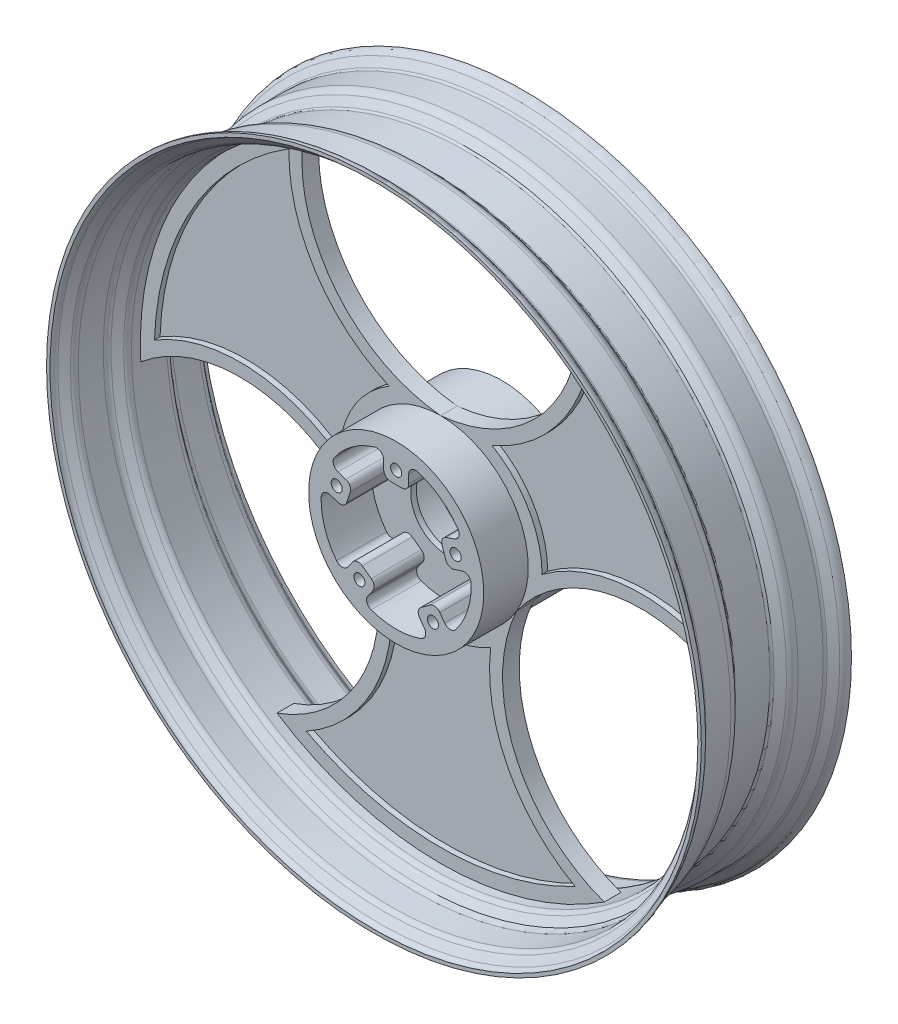
SolidWorks part; units mm, degrees
ref_plane "Front Plane" through (0, 0, 0) normal (0, 0, 1) x (1, 0, 0)
ref_plane "Top Plane" through (0, 0, 0) normal (0, 1, 0) x (1, 0, 0)
ref_plane "Right Plane" through (0, 0, 0) normal (1, 0, 0) x (0, 0, -1)
sketch "Sketch1" plane through (0, 0, 0) normal (1, 0, 0) x (0, 0, -1)
  line L0 (0, 106.096) -> (0, -87.6732) construction
  line L1 (-108.1057, 0) -> (149.1229, 0) construction
  line L27 (-38, 0) -> (38, 0)
  line L28 (38, 0) -> (38, 63)
  line L29 (-38, 0) -> (-38, 63)
  line L30 (38, 63) -> (6, 63)
  line L31 (-38, 63) -> (-6, 63)
  line L32 (6, 63) -> (6, 216)
  line L33 (-6, 63) -> (-6, 216)
  line L34 (6, 216) -> (12.4092, 216)
  line L35 (-6, 216) -> (-12.4092, 216)
  line L36 (16.2394, 217.7861) -> (20.3744, 222.7139)
  line L37 (-16.2394, 217.7861) -> (-20.3744, 222.7139)
  line L38 (24.2046, 224.5) -> (42.2046, 224.5)
  line L39 (-24.2046, 224.5) -> (-42.2046, 224.5)
  line L40 (46.0348, 226.2861) -> (50.1698, 231.2139)
  line L41 (-46.0348, 226.2861) -> (-50.1698, 231.2139)
  line L42 (54, 233) -> (54, 235.5)
  line L43 (-54, 233) -> (-54, 235.5)
  line L44 (48.2547, 232.8209) -> (44.1197, 227.893)
  line L45 (-48.2547, 232.8209) -> (-44.1197, 227.893)
  line L46 (42.2046, 227) -> (24.2046, 227)
  line L47 (-42.2046, 227) -> (-24.2046, 227)
  line L48 (18.4592, 224.3209) -> (14.3243, 219.393)
  line L49 (-18.4592, 224.3209) -> (-14.3243, 219.393)
  line L50 (12.4092, 218.5) -> (0, 218.5)
  line L51 (-12.4092, 218.5) -> (0, 218.5)
  arc A16 (12.4092, 216) -> (16.2394, 217.7861) centre (12.4092, 221) ccw
  arc A17 (-12.4092, 216) -> (-16.2394, 217.7861) centre (-12.4092, 221) cw
  arc A18 (20.3744, 222.7139) -> (24.2046, 224.5) centre (24.2046, 219.5) cw
  arc A19 (-20.3744, 222.7139) -> (-24.2046, 224.5) centre (-24.2046, 219.5) ccw
  arc A20 (42.2046, 224.5) -> (46.0348, 226.2861) centre (42.2046, 229.5) ccw
  arc A21 (-42.2046, 224.5) -> (-46.0348, 226.2861) centre (-42.2046, 229.5) cw
  arc A22 (50.1698, 231.2139) -> (54, 233) centre (54, 228) cw
  arc A23 (-50.1698, 231.2139) -> (-54, 233) centre (-54, 228) ccw
  arc A24 (54, 235.5) -> (48.2547, 232.8209) centre (54, 228) ccw
  arc A25 (-54, 235.5) -> (-48.2547, 232.8209) centre (-54, 228) cw
  arc A26 (44.1197, 227.893) -> (42.2046, 227) centre (42.2046, 229.5) cw
  arc A27 (-44.1197, 227.893) -> (-42.2046, 227) centre (-42.2046, 229.5) ccw
  arc A28 (24.2046, 227) -> (18.4592, 224.3209) centre (24.2046, 219.5) ccw
  arc A29 (-24.2046, 227) -> (-18.4592, 224.3209) centre (-24.2046, 219.5) cw
  arc A30 (14.3243, 219.393) -> (12.4092, 218.5) centre (12.4092, 221) cw
  arc A31 (-14.3243, 219.393) -> (-12.4092, 218.5) centre (-12.4092, 221) ccw
  point P8 (0, 0)
  dimension "D2" = 76
  dimension "D11" = 5
  dimension "D1" = 2.5
  dimension "D3" = 32
  dimension "D4" = 63
  dimension "D5" = 432
  dimension "D6" = 50
  dimension "D7" = 54
  dimension "D8" = 18
  dimension "D9" = 8.5
  dimension "D10" = 8.5
revolve "Revolve1" add sketch "Sketch1" angle 360 about L1
sketch "Sketch2" plane through (0, 0, 6) normal (0, 0, 1) x (1, 0, 0)
  line L0 (0, 278.9193) -> (0, -275.6484) construction
  arc A0 (0, 63) -> (98, 192.489) centre (-10.1738, 172.5285) ccw
  circle A2 centre (0, 0) radius 63 construction
  circle A3 centre (0, 0) radius 216 construction
  arc A4 (0, 63) -> (-98, 192.489) centre (10.1738, 172.5285) cw
  arc A5 (-98, 192.489) -> (98, 192.489) centre (0, 0) cw
  dimension "D1" = 110
  dimension "D2" = 196
extrude "Cut-Extrude1" cut sketch "Sketch2" against normal up to next
pattern_circular "CirPattern1" count 3 over 360 about axis through (0, 0, 108.1057) along (0, 0, 1) of "Cut-Extrude1" reverse direction yes
sketch "Sketch3" plane through (0, 0, 6) normal (0, 0, 1) x (1, 0, 0)
  line L0 (-178.4012, 103) -> (0, 0) construction
  line L1 (0, 0) -> (0, 162.2188) construction
  arc A0 (-205.8745, 7.1893) -> (-109.1634, 174.6979) centre (0, 0) cw
  arc A1 (-109.1634, 174.6979) -> (-37.0383, 62.906) centre (10.1738, 172.5285) ccw
  arc A2 (-205.8745, 7.1893) -> (-72.9973, 0.6231) centre (-144.3271, -95.0751) cw
  arc A3 (-72.9973, 0.6231) -> (-37.0383, 62.906) centre (0, 0) cw
  circle A4 centre (0, 0) radius 63 construction
  arc A8 (-54.5596, -31.5) -> (-215.7003, -11.374) centre (-144.3271, -95.0751) ccw construction
  arc A9 (-98, 192.489) -> (0, 63) centre (10.1738, 172.5285) ccw construction
  dimension "D3" = 206
  dimension "D2" = 73
  dimension "D1" = 56
  dimension "D4" = 60
extrude "Cut-Extrude2" cut sketch "Sketch3" against normal blind 4
pattern_circular "CirPattern2" count 3 over 360 about axis through (0, 0, 108.1057) along (0, 0, 1) of "Cut-Extrude2" reverse direction yes
mirror "Mirror1" about plane through (0, 0, 0) normal (0, 0, 1) of "Cut-Extrude2", "CirPattern2"
sketch "Sketch4" plane through (0, 0, 38) normal (0, 0, 1) x (1, 0, 0)
  circle A0 centre (0, 0) radius 54
  dimension "D1" = 108
extrude "Cut-Extrude3" cut sketch "Sketch4" against normal up to surface (40 mm away) up to face at (-117.5445, 67.8644, 2)
mirror "Mirror4" about plane through (0, 0, 0) normal (0, 0, 1) of "Cut-Extrude3"
sketch "Sketch5" plane through (0, 0, 2) normal (0, 0, 1) x (1, 0, 0)
  circle A0 centre (0, 0) radius 25.5
  dimension "D1" = 51
extrude "Cut-Extrude4" cut sketch "Sketch5" against normal blind 241
sketch "Sketch6" plane through (0, 0, 38) normal (0, 0, 1) x (1, 0, 0)
  line L0 (0, 54) -> (0, 0) construction
  line L1 (-9, 36) -> (9, 36)
  line L2 (-9, 36) -> (-9, 53.2447)
  line L3 (9, 36) -> (9, 53.2447)
  arc A0 (9, 53.2447) -> (-9, 53.2447) centre (0, 0) ccw
  circle A1 centre (0, 0) radius 54 construction
  point P9 (0, 36)
  dimension "D1" = 36
  dimension "D2" = 18
extrude "Boss-Extrude1" add sketch "Sketch6" against normal up to next
sketch "Sketch7" plane through (0, 0, 38) normal (0, 0, 1) x (1, 0, 0)
  circle A0 centre (0, 45) radius 4
  circle A1 centre (0, 0) radius 45 construction
  dimension "D2" = 8
  dimension "D1" = 90
extrude "Cut-Extrude5" cut sketch "Sketch7" against normal blind 25
pattern_circular "CirPattern4" count 5 over 360 about axis through (0, 0, -150.7351) along (0, 0, 1) of "Cut-Extrude5", "Boss-Extrude1" reverse direction yes
fillet "Fillet1" radius 5 20 edges at (-53.4199, 7.894, 20) (24.0153, -48.3659, 20) (9, 53.2447, 20) (-38.5776, -37.7858, 20) (38.5776, -37.7858, 20) (28.4414, -23.8345, 20) (47.8576, 25.013, 20) (53.4199, 7.894, 20) (13.8791, -34.4147, 20) (31.4569, 19.6841, 20) (37.0192, 2.5651, 20) (9, 36, 20) (-9, 53.2447, 20) (-9, 36, 20) (-24.0153, -48.3659, 20) (-13.8791, -34.4147, 20) (-28.4414, -23.8345, 20) (-37.0192, 2.5651, 20) (-47.8576, 25.013, 20) (-31.4569, 19.6841, 20)
